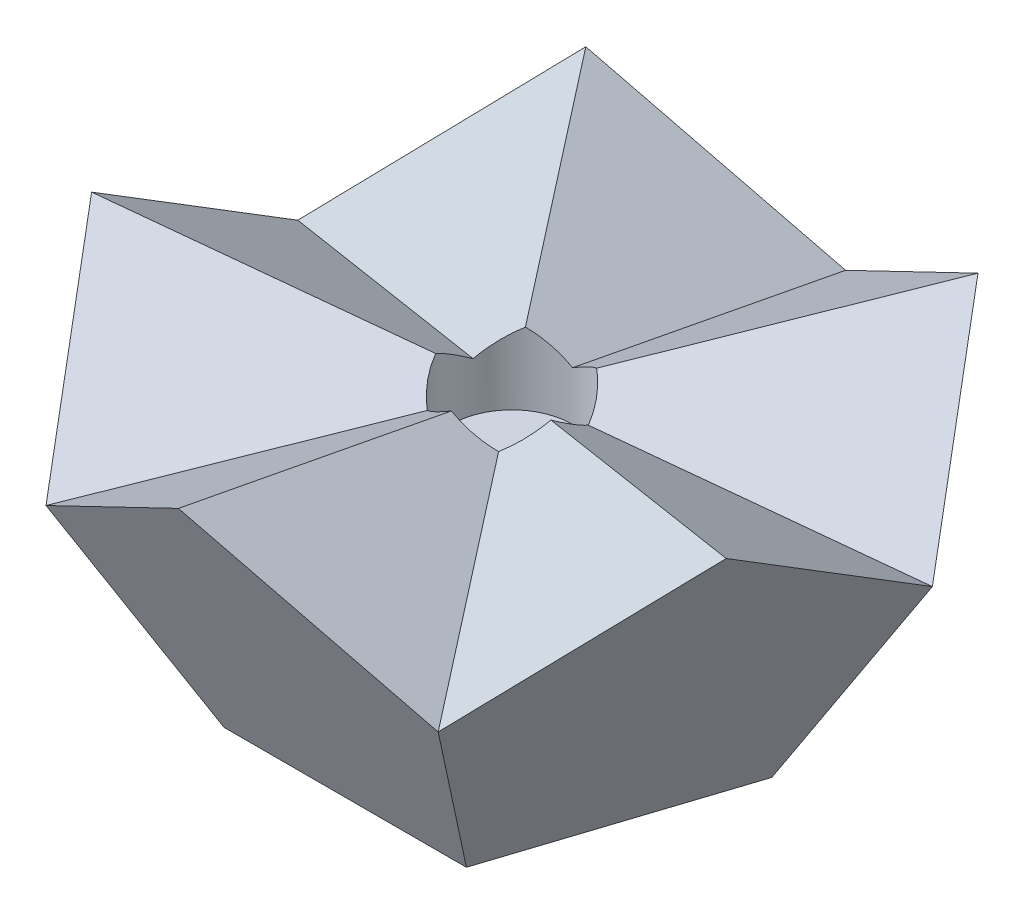
SolidWorks part; units mm, degrees
ref_plane "Front Plane" through (0, 0, 0) normal (0, 0, 1) x (1, 0, 0)
ref_plane "Top Plane" through (0, 0, 0) normal (0, 1, 0) x (1, 0, 0)
ref_plane "Right Plane" through (0, 0, 0) normal (1, 0, 0) x (0, 0, -1)
ref_axis "Axis1" through (0, 18.3541, 0) along (0, -1, 0)
sketch "Sketch2" plane through (0, 0, 0) normal (0, 1, 0) x (1, 0, 0)
  line L1 (0, 10.8033) -> (-10.2745, 3.3384)
  line L2 (-10.2745, 3.3384) -> (-6.35, -8.74)
  line L3 (-6.35, -8.74) -> (6.35, -8.74)
  line L4 (6.35, -8.74) -> (10.2745, 3.3384)
  line L5 (10.2745, 3.3384) -> (0, 10.8033)
  circle A0 centre (0, 0) radius 8.74 construction
  dimension "D1" = 12.7
extrude "Boss-Extrude1" add sketch "Sketch2" along normal blind 12.7 draft 31.717
mirror "Mirror1" about plane through (10.2745, 0, -3.3384) normal (0.5, 0.5257, -0.6882) of "Boss-Extrude1"
mirror "Mirror3" about plane through (-10.2745, 0, -3.3384) normal (-0.809, 0.5257, 0.2629) of "Boss-Extrude1"
mirror "Mirror4" about plane through (0, 0, -10.8033) normal (-0.5, 0.5257, -0.6882) of "Boss-Extrude1"
mirror "Mirror5" about plane through (-6.35, 0, 8.74) normal (0, 0.5257, 0.8507) of "Boss-Extrude1"
mirror "Mirror6" about plane through (6.35, 0, 8.74) normal (0.809, 0.5257, 0.2629) of "Boss-Extrude1"
sketch "Sketch3" plane through (-6.0148, 10.233, -1.9543) normal (-0.5, 0.8507, -0.1625) x (0.866, 0.4911, -0.0938)
  line L0 (6.9453, -0.8387) -> (8.1548, -1.3006) construction
  point P0 (7.55, -1.0697)
ref_plane "Plane1" through (0.5237, 14.1417, -1.6118) normal (0, -1, 0) x (-1, 0, 0)
sketch "Sketch4" plane through (0.5237, 14.1417, -1.6118) normal (0, -1, 0) x (-1, 0, 0)
  circle A0 centre (0.5237, -1.6118) radius 3.175
  dimension "D1" = 6.35
extrude "Cut-Extrude1" cut sketch "Sketch4" against normal through all and the other way blind 3.175
equation "\"angle between faces\"= arccos ( - sqr ( 5 ) / 5 )"
equation "\"edges per side\"= 5"
equation "\"edge\"= .5"
equation "\"D1@Sketch2\"=\"edge\""
equation "\"D3@Boss-Extrude1\"=(180-\"angle between faces\")/2"
equation "\"D1@Boss-Extrude1\"=\"edge\""
